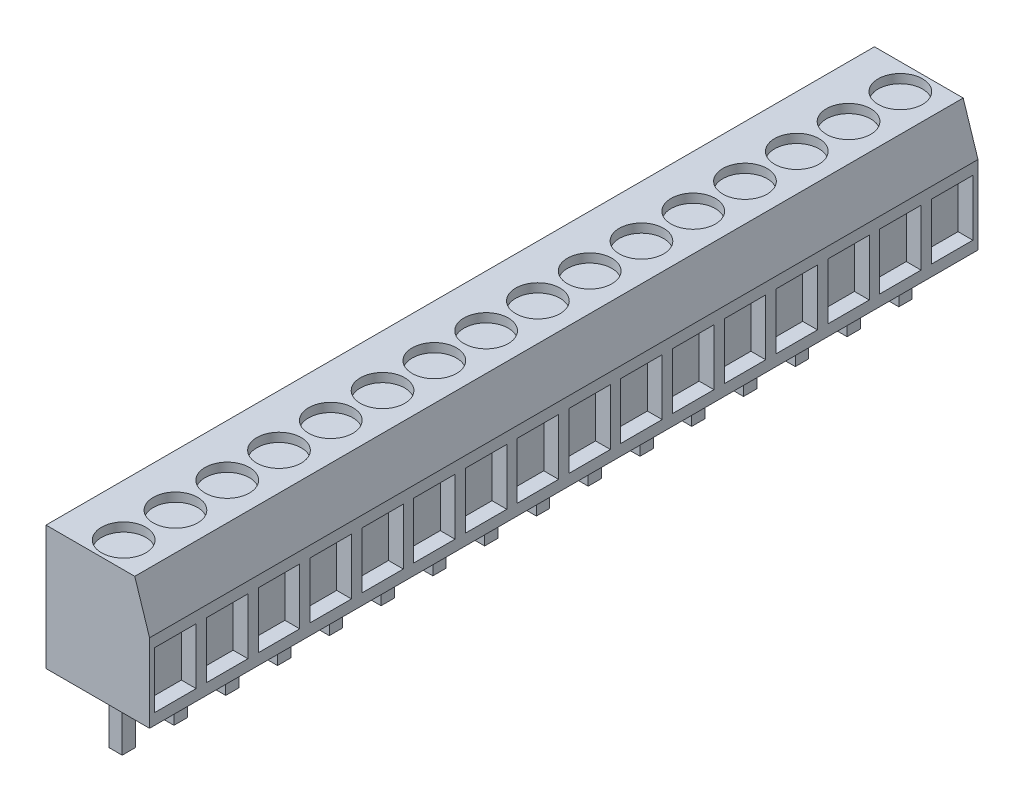
SolidWorks part; units mm, degrees
ref_plane "Front Plane" through (0, 0, 0) normal (0, 0, 1) x (1, 0, 0)
ref_plane "Top Plane" through (0, 0, 0) normal (0, 1, 0) x (1, 0, 0)
ref_plane "Right Plane" through (0, 0, 0) normal (1, 0, 0) x (0, 0, -1)
sketch "Sketch2" plane through (0, 0, 0) normal (0, 0, 1) x (1, 0, 0)
  line L0 (0, 0) -> (0, 8.4)
  line L3 (0, 8.4) -> (6, 8.4)
  line L4 (6, 8.4) -> (7, 5.3)
  line L5 (7, 5.3) -> (7, 0)
  line L6 (7, 0) -> (0, 0)
  point P2 (0, 0)
  point P3 (0, 8.4)
  point P4 (0, 4.4)
  point P9 (0, 8.2596)
  dimension "D1" = 6
  dimension "D2" = 7
  dimension "D3" = 8.4
  dimension "D4" = 5.3
extrude "Boss-Extrude1" add sketch "Sketch2" against normal blind 56
sketch "Sketch3" plane through (0, 8.4, 0) normal (0, 1, 0) x (1, 0, 0)
  line L0 (3.5, 56) -> (3.5, 0) construction
  line L3 (3.5, 1.75) -> (3.5, 5.25) construction
  line L4 (0, 56) -> (0, 0) construction
  line L7 (6, 0) -> (0, 0) construction
  circle A0 centre (3.5, 1.75) radius 1.5
  circle A1 centre (3.5, 5.25) radius 1.5
  circle A2 centre (3.5, 8.75) radius 1.5
  circle A3 centre (3.5, 12.25) radius 1.5
  circle A4 centre (3.5, 15.75) radius 1.5
  circle A5 centre (3.5, 19.25) radius 1.5
  circle A6 centre (3.5, 22.75) radius 1.5
  circle A7 centre (3.5, 26.25) radius 1.5
  circle A8 centre (3.5, 29.75) radius 1.5
  circle A9 centre (3.5, 33.25) radius 1.5
  circle A10 centre (3.5, 36.75) radius 1.5
  circle A11 centre (3.5, 40.25) radius 1.5
  circle A12 centre (3.5, 43.75) radius 1.5
  circle A13 centre (3.5, 47.25) radius 1.5
  circle A14 centre (3.5, 50.75) radius 1.5
  circle A15 centre (3.5, 54.25) radius 1.5
  point P2 (3.5, 0.724)
  point P3 (3.5, 0)
  dimension "D4" = 3
  dimension "D2" = 3.5
  dimension "D3" = 1.75
  dimension "D5" = 3.5
  dimension "D1" = 16
extrude "Cut-Extrude1" cut sketch "Sketch3" against normal blind 0.6
sketch "Sketch4" plane through (7, 0, 0) normal (1, 0, 0) x (0, 0, -1)
  line L0 (3.85, 0.75) -> (6.65, 0.75)
  line L1 (0.35, 0.75) -> (3.15, 0.75)
  line L2 (0.35, 0.75) -> (0.35, 4.55)
  line L3 (0.35, 4.55) -> (3.15, 4.55)
  line L4 (3.15, 0.75) -> (3.15, 4.55)
  line L5 (3.85, 0.75) -> (3.85, 4.55)
  line L6 (3.85, 4.55) -> (6.65, 4.55)
  line L7 (6.65, 0.75) -> (6.65, 4.55)
  line L8 (7.35, 0.75) -> (10.15, 0.75)
  line L9 (7.35, 0.75) -> (7.35, 4.55)
  line L10 (7.35, 4.55) -> (10.15, 4.55)
  line L11 (10.15, 0.75) -> (10.15, 4.55)
  line L12 (10.85, 0.75) -> (13.65, 0.75)
  line L13 (10.85, 0.75) -> (10.85, 4.55)
  line L14 (10.85, 4.55) -> (13.65, 4.55)
  line L15 (13.65, 0.75) -> (13.65, 4.55)
  line L16 (14.35, 0.75) -> (17.15, 0.75)
  line L17 (14.35, 0.75) -> (14.35, 4.55)
  line L18 (14.35, 4.55) -> (17.15, 4.55)
  line L19 (17.15, 0.75) -> (17.15, 4.55)
  line L20 (17.85, 0.75) -> (20.65, 0.75)
  line L21 (17.85, 0.75) -> (17.85, 4.55)
  line L22 (17.85, 4.55) -> (20.65, 4.55)
  line L23 (20.65, 0.75) -> (20.65, 4.55)
  line L24 (21.35, 0.75) -> (24.15, 0.75)
  line L25 (21.35, 0.75) -> (21.35, 4.55)
  line L26 (21.35, 4.55) -> (24.15, 4.55)
  line L27 (24.15, 0.75) -> (24.15, 4.55)
  line L28 (24.85, 0.75) -> (27.65, 0.75)
  line L29 (24.85, 0.75) -> (24.85, 4.55)
  line L30 (24.85, 4.55) -> (27.65, 4.55)
  line L31 (27.65, 0.75) -> (27.65, 4.55)
  line L32 (28.35, 0.75) -> (31.15, 0.75)
  line L33 (28.35, 0.75) -> (28.35, 4.55)
  line L34 (28.35, 4.55) -> (31.15, 4.55)
  line L35 (31.15, 0.75) -> (31.15, 4.55)
  line L36 (31.85, 0.75) -> (34.65, 0.75)
  line L37 (31.85, 0.75) -> (31.85, 4.55)
  line L38 (31.85, 4.55) -> (34.65, 4.55)
  line L39 (34.65, 0.75) -> (34.65, 4.55)
  line L40 (35.35, 0.75) -> (38.15, 0.75)
  line L41 (35.35, 0.75) -> (35.35, 4.55)
  line L42 (35.35, 4.55) -> (38.15, 4.55)
  line L43 (38.15, 0.75) -> (38.15, 4.55)
  line L44 (38.85, 0.75) -> (41.65, 0.75)
  line L45 (38.85, 0.75) -> (38.85, 4.55)
  line L46 (38.85, 4.55) -> (41.65, 4.55)
  line L47 (41.65, 0.75) -> (41.65, 4.55)
  line L48 (42.35, 0.75) -> (45.15, 0.75)
  line L49 (42.35, 0.75) -> (42.35, 4.55)
  line L50 (42.35, 4.55) -> (45.15, 4.55)
  line L51 (45.15, 0.75) -> (45.15, 4.55)
  line L52 (45.85, 0.75) -> (48.65, 0.75)
  line L53 (45.85, 0.75) -> (45.85, 4.55)
  line L54 (45.85, 4.55) -> (48.65, 4.55)
  line L55 (48.65, 0.75) -> (48.65, 4.55)
  line L56 (49.35, 0.75) -> (52.15, 0.75)
  line L57 (49.35, 0.75) -> (49.35, 4.55)
  line L58 (49.35, 4.55) -> (52.15, 4.55)
  line L59 (52.15, 0.75) -> (52.15, 4.55)
  line L60 (52.85, 0.75) -> (55.65, 0.75)
  line L61 (52.85, 0.75) -> (52.85, 4.55)
  line L62 (52.85, 4.55) -> (55.65, 4.55)
  line L63 (55.65, 0.75) -> (55.65, 4.55)
  line L64 (0.35, 0.75) -> (3.85, 0.75) construction
  line L65 (1.75, 2.65) -> (0, 2.65) construction
  line L66 (0, 0) -> (0, 5.3) construction
  line L67 (1.75, 4.55) -> (1.75, 0.75) construction
  point P72 (2.3819, 2.2)
  dimension "D1" = 2.8
  dimension "D2" = 3.8
  dimension "D4" = 3.5
  dimension "D5" = 1.75
  dimension "D3" = 16
extrude "Cut-Extrude2" cut sketch "Sketch4" against normal blind 1
sketch "Sketch5" plane through (0, 0, 0) normal (0, -1, 0) x (1, 0, 0)
  line L0 (3.4, 0) -> (3.4, -56) construction
  line L1 (0, 0) -> (7, 0) construction
  line L2 (0, -56) -> (7, -56) construction
  line L3 (3.4, -1.3) -> (3.4, -2.2) construction
  line L4 (2.95, -1.3) -> (3.85, -1.3)
  line L5 (2.95, -1.3) -> (2.95, -2.2)
  line L6 (2.95, -2.2) -> (3.85, -2.2)
  line L7 (3.85, -1.3) -> (3.85, -2.2)
  line L8 (3.85, -1.75) -> (2.95, -1.75) construction
  line L9 (0, -56) -> (0, 0) construction
  line L14 (3.85, -5.25) -> (2.95, -5.25) construction
  line L15 (2.95, -4.8) -> (2.95, -5.7)
  line L16 (2.95, -4.8) -> (3.85, -4.8)
  line L21 (3.85, -4.8) -> (3.85, -5.7)
  line L22 (2.95, -5.7) -> (3.85, -5.7)
  line L23 (3.85, -8.75) -> (2.95, -8.75) construction
  line L28 (2.95, -8.3) -> (2.95, -9.2)
  line L29 (2.95, -8.3) -> (3.85, -8.3)
  line L30 (3.85, -8.3) -> (3.85, -9.2)
  line L35 (2.95, -9.2) -> (3.85, -9.2)
  line L36 (3.85, -12.25) -> (2.95, -12.25) construction
  line L37 (2.95, -11.8) -> (2.95, -12.7)
  line L42 (2.95, -11.8) -> (3.85, -11.8)
  line L43 (3.85, -11.8) -> (3.85, -12.7)
  line L44 (2.95, -12.7) -> (3.85, -12.7)
  line L49 (3.85, -15.75) -> (2.95, -15.75) construction
  line L50 (2.95, -15.3) -> (2.95, -16.2)
  line L51 (2.95, -15.3) -> (3.85, -15.3)
  line L56 (3.85, -15.3) -> (3.85, -16.2)
  line L57 (2.95, -16.2) -> (3.85, -16.2)
  line L58 (3.85, -19.25) -> (2.95, -19.25) construction
  line L63 (2.95, -18.8) -> (2.95, -19.7)
  line L64 (2.95, -18.8) -> (3.85, -18.8)
  line L65 (3.85, -18.8) -> (3.85, -19.7)
  line L70 (2.95, -19.7) -> (3.85, -19.7)
  line L71 (3.85, -22.75) -> (2.95, -22.75) construction
  line L72 (2.95, -22.3) -> (2.95, -23.2)
  line L77 (2.95, -22.3) -> (3.85, -22.3)
  line L78 (3.85, -22.3) -> (3.85, -23.2)
  line L79 (2.95, -23.2) -> (3.85, -23.2)
  line L84 (3.85, -26.25) -> (2.95, -26.25) construction
  line L85 (2.95, -25.8) -> (2.95, -26.7)
  line L86 (2.95, -25.8) -> (3.85, -25.8)
  line L91 (3.85, -25.8) -> (3.85, -26.7)
  line L92 (2.95, -26.7) -> (3.85, -26.7)
  line L93 (3.85, -29.75) -> (2.95, -29.75) construction
  line L98 (2.95, -29.3) -> (2.95, -30.2)
  line L99 (2.95, -29.3) -> (3.85, -29.3)
  line L100 (3.85, -29.3) -> (3.85, -30.2)
  line L105 (2.95, -30.2) -> (3.85, -30.2)
  line L106 (3.85, -33.25) -> (2.95, -33.25) construction
  line L107 (2.95, -32.8) -> (2.95, -33.7)
  line L112 (2.95, -32.8) -> (3.85, -32.8)
  line L113 (3.85, -32.8) -> (3.85, -33.7)
  line L114 (2.95, -33.7) -> (3.85, -33.7)
  line L115 (3.85, -36.75) -> (2.95, -36.75) construction
  line L116 (2.95, -36.3) -> (2.95, -37.2)
  line L117 (2.95, -36.3) -> (3.85, -36.3)
  line L118 (3.85, -36.3) -> (3.85, -37.2)
  line L119 (2.95, -37.2) -> (3.85, -37.2)
  line L120 (3.85, -40.25) -> (2.95, -40.25) construction
  line L121 (2.95, -39.8) -> (2.95, -40.7)
  line L122 (2.95, -39.8) -> (3.85, -39.8)
  line L123 (3.85, -39.8) -> (3.85, -40.7)
  line L124 (2.95, -40.7) -> (3.85, -40.7)
  line L125 (3.85, -43.75) -> (2.95, -43.75) construction
  line L126 (2.95, -43.3) -> (2.95, -44.2)
  line L127 (2.95, -43.3) -> (3.85, -43.3)
  line L128 (3.85, -43.3) -> (3.85, -44.2)
  line L129 (2.95, -44.2) -> (3.85, -44.2)
  line L130 (3.85, -47.25) -> (2.95, -47.25) construction
  line L131 (2.95, -46.8) -> (2.95, -47.7)
  line L132 (2.95, -46.8) -> (3.85, -46.8)
  line L133 (3.85, -46.8) -> (3.85, -47.7)
  line L134 (2.95, -47.7) -> (3.85, -47.7)
  line L135 (3.85, -50.75) -> (2.95, -50.75) construction
  line L136 (2.95, -50.3) -> (2.95, -51.2)
  line L137 (2.95, -50.3) -> (3.85, -50.3)
  line L138 (3.85, -50.3) -> (3.85, -51.2)
  line L139 (2.95, -51.2) -> (3.85, -51.2)
  line L140 (3.85, -54.25) -> (2.95, -54.25) construction
  line L141 (2.95, -53.8) -> (2.95, -54.7)
  line L142 (2.95, -53.8) -> (3.85, -53.8)
  line L143 (3.85, -53.8) -> (3.85, -54.7)
  line L144 (2.95, -54.7) -> (3.85, -54.7)
  line L145 (3.85, -1.75) -> (3.85, -5.25) construction
  point P16 (3.4, -1.75)
  point P110 (3.4, -5.25)
  point P111 (3.4, -8.75)
  point P112 (3.4, -12.25)
  point P113 (3.4, -15.75)
  point P114 (3.4, -19.25)
  point P115 (3.4, -22.75)
  point P116 (3.4, -26.25)
  point P117 (3.4, -29.75)
  point P118 (3.4, -33.25)
  point P119 (3.4, -36.75)
  point P120 (3.4, -40.25)
  point P121 (3.4, -43.75)
  point P122 (3.4, -47.25)
  point P123 (3.4, -50.75)
  point P124 (3.4, -54.25)
  dimension "D1" = 3.4
  dimension "D2" = 0.9
  dimension "D3" = 1.75
  dimension "D5" = 3.5
  dimension "D4" = 16
extrude "Boss-Extrude2" add sketch "Sketch5" along normal blind 3.8 separate body
ref_axis "Axis1" through (3.4, 0, -1.75) along (0, -1, 0)
ref_axis "Axis2" through (3.4, 0, -54.25) along (0, -1, 0)
ref_plane "mid-plane" through (0, 0, -28) normal (0, 0, 1) x (1, 0, 0)
